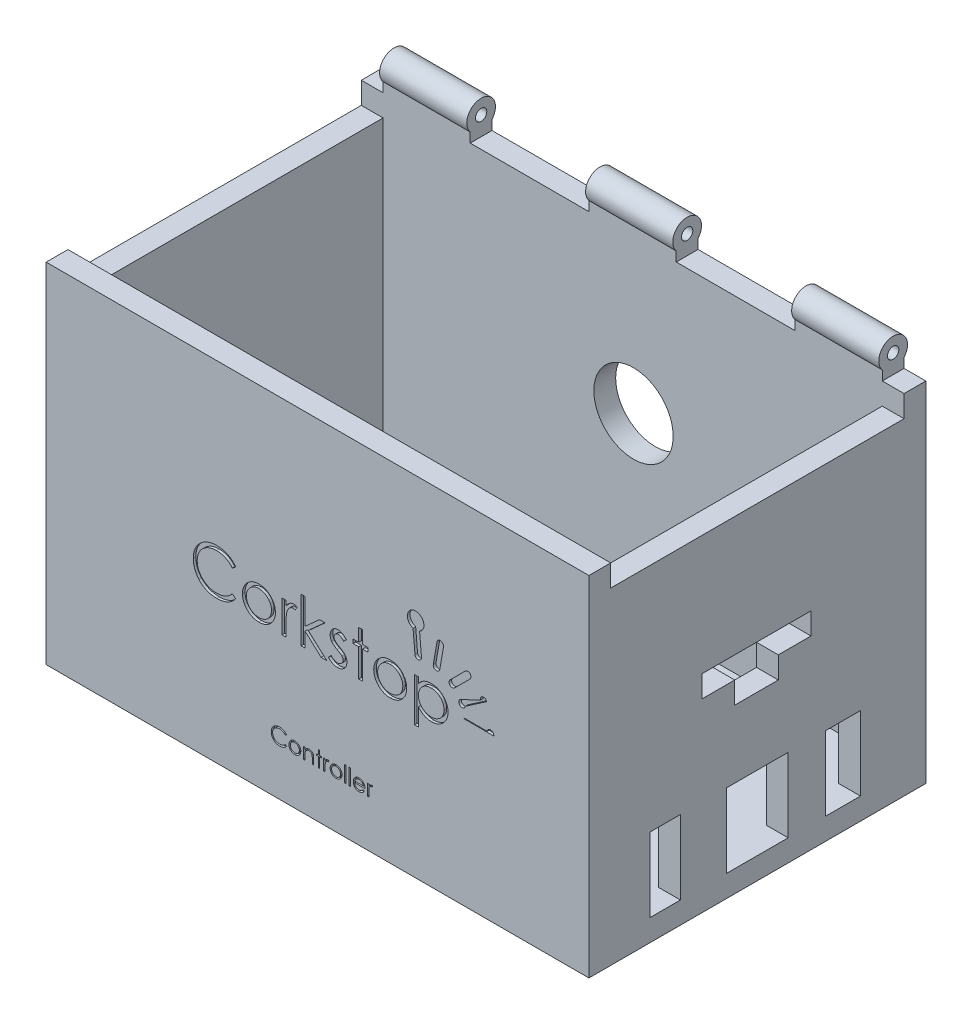
SolidWorks part; units mm, degrees
ref_plane "Front Plane" through (0, 0, 0) normal (0, 0, 1) x (1, 0, 0)
ref_plane "Top Plane" through (0, 0, 0) normal (0, 1, 0) x (1, 0, 0)
ref_plane "Right Plane" through (0, 0, 0) normal (1, 0, 0) x (0, 0, -1)
sketch "Sketch1" plane through (0, 0, 0) normal (0, 1, 0) x (1, 0, 0)
  line L1 (-79.1, 49.1) -> (79.1, 49.1)
  line L2 (-79.1, 49.1) -> (-79.1, -49.1)
  line L3 (-79.1, -49.1) -> (79.1, -49.1)
  line L4 (79.1, 49.1) -> (79.1, -49.1)
  line L5 (-79.1, 49.1) -> (79.1, -49.1) construction
  line L6 (-79.1, -49.1) -> (79.1, 49.1) construction
  point P0 (0, 0)
  dimension "D1" = 158.2
  dimension "D2" = 98.2
extrude "Boss-Extrude1" add sketch "Sketch1" along normal blind 6.35
sketch "Sketch2" plane through (0, 0, 49.1) normal (0, 0, 1) x (1, 0, 0)
  line L1 (-79.1, 101.6) -> (79.1, 101.6)
  line L2 (-79.1, 101.6) -> (-79.1, 6.35)
  line L3 (-79.1, 6.35) -> (79.1, 6.35)
  line L4 (79.1, 101.6) -> (79.1, 6.35)
  line L5 (-79.1, 101.6) -> (79.1, 6.35) construction
  line L6 (-79.1, 6.35) -> (79.1, 101.6) construction
  point P0 (0, 53.975)
  dimension "D1" = 95.25
extrude "Boss-Extrude2" add sketch "Sketch2" against normal blind 6.35
sketch "Sketch3" plane through (-79.1, 0, 0) normal (-1, 0, 0) x (0, 0, 1)
  line L1 (-42.75, 101.6) -> (42.75, 101.6)
  line L2 (-42.75, 101.6) -> (-42.75, 6.35)
  line L3 (-42.75, 6.35) -> (42.75, 6.35)
  line L4 (42.75, 101.6) -> (42.75, 6.35)
  line L5 (-42.75, 101.6) -> (42.75, 6.35) construction
  line L6 (-42.75, 6.35) -> (42.75, 101.6) construction
  point P0 (0, 53.975)
  dimension "D1" = 95.25
extrude "Boss-Extrude3" add sketch "Sketch3" against normal blind 6.35
sketch "Sketch4" plane through (0, 0, -49.1) normal (0, 0, -1) x (-1, 0, 0)
  line L1 (-79.1, 101.6) -> (79.1, 101.6)
  line L2 (-79.1, 101.6) -> (-79.1, 6.35)
  line L3 (-79.1, 6.35) -> (79.1, 6.35)
  line L4 (79.1, 101.6) -> (79.1, 6.35)
  line L5 (-79.1, 101.6) -> (79.1, 6.35) construction
  line L6 (-79.1, 6.35) -> (79.1, 101.6) construction
  point P0 (0, 53.975)
  dimension "D1" = 95.25
extrude "Boss-Extrude4" add sketch "Sketch4" against normal blind 6.35
sketch "Sketch5" plane through (79.1, 0, 0) normal (1, 0, 0) x (0, 0, -1)
  line L0 (42.75, 101.6) -> (42.75, 6.35) construction
  line L1 (-42.75, 27.94) -> (42.75, 27.94)
  line L2 (-42.75, 27.94) -> (-42.75, 101.6)
  line L3 (-42.75, 101.6) -> (42.75, 101.6)
  line L4 (42.75, 27.94) -> (42.75, 101.6)
  line L5 (-42.75, 27.94) -> (42.75, 101.6) construction
  line L6 (-42.75, 101.6) -> (42.75, 27.94) construction
  line L7 (42.75, 101.6) -> (42.75, 6.35) construction
  line L8 (42.75, 101.6) -> (49.1, 101.6) construction
  point P0 (0, 64.77)
  dimension "D1" = 73.66
  dimension "D2" = 0
extrude "Boss-Extrude5" add sketch "Sketch5" against normal blind 6.35
sketch "Sketch6" plane through (79.1, 0, 0) normal (1, 0, 0) x (0, 0, -1)
  line L0 (-42.75, 27.94) -> (42.75, 27.94) construction
  line L1 (-22.43, 27.94) -> (-8.968, 27.94)
  line L2 (-22.43, 27.94) -> (-22.43, 6.35)
  line L3 (-22.43, 6.35) -> (-8.968, 6.35)
  line L4 (-8.968, 27.94) -> (-8.968, 6.35)
  line L5 (-42.75, 6.35) -> (42.75, 6.35) construction
  line L6 (42.75, 6.35) -> (-42.75, 6.35) construction
  line L7 (8.968, 27.94) -> (19.89, 27.94)
  line L8 (8.968, 27.94) -> (8.968, 6.35)
  line L9 (8.968, 6.35) -> (19.89, 6.35)
  line L10 (19.89, 27.94) -> (19.89, 6.35)
  line L11 (-42.75, 6.35) -> (-42.75, 27.94) construction
  line L12 (42.75, 27.94) -> (42.75, 6.35) construction
  line L14 (-42.75, 27.94) -> (-31.32, 27.94)
  line L15 (-42.75, 27.94) -> (-42.75, 6.35)
  line L16 (-42.75, 6.35) -> (-31.32, 6.35)
  line L17 (-31.32, 27.94) -> (-31.32, 6.35)
  line L18 (42.75, 27.94) -> (30.05, 27.94)
  line L19 (42.75, 27.94) -> (42.75, 6.35)
  line L20 (42.75, 6.35) -> (30.05, 6.35)
  line L21 (30.05, 27.94) -> (30.05, 6.35)
  dimension "D1" = 13.462
  dimension "D2" = 10.922
  dimension "D3" = 20.32
  dimension "D4" = 22.86
  dimension "D5" = 0
  dimension "D6" = 11.43
  dimension "D7" = 12.7
  dimension "D8" = 17.936
extrude "Boss-Extrude6" add sketch "Sketch6" against normal blind 6.35
sketch "Çizim2" plane through (79.1, 0, 0) normal (1, 0, 0) x (0, 0, -1)
  line L0 (-49.1, 0) -> (49.1, 0) construction
  line L1 (-16.125, 60.325) -> (15.625, 60.325)
  line L2 (-16.125, 60.325) -> (-16.125, 53.975)
  line L3 (-16.125, 53.975) -> (-6.6, 53.975)
  line L4 (15.625, 60.325) -> (15.625, 53.975)
  line L5 (-16.125, 60.325) -> (15.625, 53.975) construction
  line L6 (-16.125, 53.975) -> (15.625, 60.325) construction
  line L7 (-42.75, 101.6) -> (-42.75, 6.35) construction
  line L8 (6.1, 53.975) -> (15.625, 53.975)
  line L9 (-6.6, 47.625) -> (6.1, 47.625)
  line L10 (-6.6, 47.625) -> (-6.6, 53.975)
  line L12 (6.1, 47.625) -> (6.1, 53.975)
  line L13 (-6.6, 47.625) -> (-0.25, 50.8) construction
  line L14 (-6.6, 53.975) -> (6.1, 47.625) construction
  point P0 (-0.25, 57.15)
  point P9 (-0.25, 50.8)
  dimension "D1" = 60.325
  dimension "D2" = 53.975
  dimension "D3" = 31.75
  dimension "D4" = 42.5
  dimension "D5" = 12.7
  dimension "D6" = 42.5
  dimension "D7" = 6.35
extrude "Kes-Ekstrüzyon1" cut sketch "Çizim2" against normal blind 6.35
sketch "Çizim3" plane through (0, 0, -49.1) normal (0, 0, -1) x (-1, 0, 0)
  line L0 (-79.1, 0) -> (79.1, 0) construction
  line L1 (-79.1, 101.6) -> (-79.1, 0) construction
  circle A0 centre (-0.25, 57.15) radius 11.557
  dimension "D1" = 23.114
  dimension "D2" = 57.15
  dimension "D3" = 78.85
extrude "Kes-Ekstrüzyon2" cut sketch "Çizim3" against normal blind 6.35
sketch "Çizim4" plane through (-79.1, 0, 0) normal (-1, 0, 0) x (0, 0, 1)
  line L0 (-49.1, 0) -> (49.1, 0) construction
  circle A0 centre (0, 41.275) radius 4.826
  dimension "D1" = 41.275
extrude "Kes-Ekstrüzyon3" cut sketch "Çizim4" against normal blind 6.35
sketch "Çizim5" plane through (79.1, 0, 0) normal (1, 0, 0) x (0, 0, -1)
  line L0 (42.75, 6.35) -> (42.75, 101.6) construction
  line L1 (-42.75, 101.6) -> (42.75, 101.6)
  line L2 (-42.75, 101.6) -> (-42.75, 95.25)
  line L3 (-42.75, 95.25) -> (42.75, 95.25)
  line L4 (42.75, 101.6) -> (42.75, 95.25)
  dimension "D1" = 6.35
extrude "Kes-Ekstrüzyon4" cut sketch "Çizim5" against normal blind 6.35
sketch "Çizim6" plane through (-79.1, 0, 0) normal (-1, 0, 0) x (0, 0, 1)
  line L1 (-42.75, 101.6) -> (42.75, 101.6)
  line L2 (-42.75, 101.6) -> (-42.75, 95.25)
  line L3 (-42.75, 95.25) -> (42.75, 95.25)
  line L4 (42.75, 101.6) -> (42.75, 95.25)
extrude "Kes-Ekstrüzyon5" cut sketch "Çizim6" against normal blind 6.35
sketch "Çizim7" plane through (0, 0, 49.1) normal (0, 0, 1) x (1, 0, 0)
  line L0 (-72.75, 6.35) -> (-72.75, 95.25) construction
  line L1 (-72.75, 6.35) -> (72.75, 6.35) construction
  text T0 "Corkstop" font "Century Gothic" height 12.7
  dimension "D1" = 35.56
  dimension "D2" = 35.56
extrude "Kes-Ekstrüzyon6" cut sketch "Çizim7" against normal blind 0.762
sketch "Çizim12" plane through (0, 0, 49.1) normal (0, 0, 1) x (1, 0, 0)
  line L2 (27.8371, 62.676) -> (28.3905, 56.3502)
  line L4 (29.7431, 62.8428) -> (30.2966, 56.517)
  arc A1 (28.3905, 56.3502) -> (30.2966, 56.517) centre (29.3435, 56.4336) ccw
  arc A2 (29.7431, 62.8428) -> (27.8371, 62.676) centre (28.5971, 64.966) ccw
  dimension "D1" = 3.81
  dimension "D2" = 6.35
  dimension "D3" = 1.9133
  dimension "D4" = 6.35
  dimension "D5" = 6.35
extrude "Kes-Ekstrüzyon7" cut sketch "Çizim12" against normal blind 0.762
sketch "Çizim14" plane through (0, 0, 49.1) normal (0, 0, 1) x (1, 0, 0)
  line L1 (43.1131, 47.4484) -> (49.4631, 47.4484)
  line L3 (42.4975, 47.2249) -> (51.3633, 47.2249)
  arc A0 (51.3633, 47.2249) -> (49.4631, 47.4484) centre (50.4132, 47.3366) ccw
  arc A1 (43.1131, 47.4484) -> (42.4975, 47.2249) centre (43.1131, 46.489) ccw
  dimension "D1" = 1.9133
  dimension "D2" = 6.35
  dimension "D3" = 5.08
extrude "Kes-Ekstrüzyon8" cut sketch "Çizim14" against normal blind 0.762
sketch "Çizim15" plane through (0, 0, 49.1) normal (0, 0, 1) x (1, 0, 0)
  line L0 (41.7144, 51.6199) -> (47.4695, 54.3035)
  line L1 (43.0621, 50.5695) -> (49.3029, 54.8505)
  line L2 (49.4631, 47.4484) -> (43.1131, 47.4484) construction
  arc A0 (49.3029, 54.8505) -> (47.4695, 54.3035) centre (48.3862, 54.577) ccw
  arc A1 (41.7144, 51.6199) -> (43.0621, 50.5695) centre (42.1199, 50.7504) ccw
  dimension "D1" = 1.9133
  dimension "D2" = 6.35
  dimension "D3" = 5.842
  dimension "D4" = 3.302
extrude "Kes-Ekstrüzyon9" cut sketch "Çizim15" against normal blind 0.762
sketch "Çizim18" plane through (0, 0, 49.1) normal (0, 0, 1) x (1, 0, 0)
  line L0 (38.6008, 54.9998) -> (43.0909, 59.4899)
  line L1 (39.8809, 53.5741) -> (44.4438, 58.137)
  arc A0 (44.4438, 58.137) -> (43.0909, 59.4899) centre (43.7674, 58.8135) ccw
  arc A1 (38.6008, 54.9998) -> (39.8809, 53.5741) centre (39.2792, 54.3214) ccw
  dimension "D1" = 1.9133
  dimension "D2" = 6.35
sketch "Çizim19" plane through (0, 0, 49.1) normal (0, 0, 1) x (1, 0, 0)
  line L0 (33.7349, 56.4717) -> (34.8376, 62.7252)
  line L1 (35.6013, 56.0381) -> (36.7218, 62.393)
  arc A0 (36.7218, 62.393) -> (34.8376, 62.7252) centre (35.7797, 62.5591) ccw
  arc A1 (33.7349, 56.4717) -> (35.6013, 56.0381) centre (34.6798, 56.3051) ccw
  dimension "D1" = 1.9133
  dimension "D2" = 6.35
extrude "Kes-Ekstrüzyon12" cut sketch "Çizim19" against normal blind 0.762
extrude "Kes-Ekstrüzyon13" cut sketch "Çizim18" against normal blind 0.762
sketch "Çizim27" plane through (0, 0, 49.1) normal (0, 0, 1) x (1, 0, 0)
  text T0 "Controller\r\n" font "Century Gothic" height 4.572
sketch "Çizim21" plane through (-72.75, 0, 0) normal (1, 0, 0) x (0, 0, -1)
  line L1 (42.75, 101.6) -> (49.1, 101.6)
  line L2 (42.75, 101.6) -> (42.75, 104.3997)
  line L4 (49.1, 101.6) -> (49.1, 104.3997)
  arc A0 (49.1, 104.3997) -> (42.75, 104.3997) centre (45.925, 107.1365) ccw
  dimension "D1" = 6.35
  dimension "D2" = 3.175
extrude "Yükseklik-Ekstrüzyon2" add sketch "Çizim21" along normal blind 25.4
sketch "Çizim22" plane through (72.75, 0, 0) normal (-1, 0, 0) x (0, 0, 1)
  line L0 (-49.1, 101.6) -> (-42.75, 101.6)
  line L1 (-49.1, 101.6) -> (-49.1, 104.3995)
  line L2 (-42.75, 101.6) -> (-42.75, 104.3995)
  arc A0 (-42.75, 104.3995) -> (-49.1, 104.3995) centre (-45.925, 107.1364) ccw
  dimension "D1" = 6.35
  dimension "D2" = 3.175
extrude "Yükseklik-Ekstrüzyon3" add sketch "Çizim22" along normal blind 25.4
ref_plane "Düzlem2" through (12.7, 0, 0) normal (-1, 0, 0) x (0, 0, 1)
sketch "Çizim23" plane through (12.7, 0, 0) normal (-1, 0, 0) x (0, 0, 1)
  line L0 (-49.1, 101.6) -> (-42.75, 101.6)
  line L1 (-49.1, 101.6) -> (-49.1, 104.3997)
  line L2 (-42.75, 101.6) -> (-42.75, 104.3997)
  arc A0 (-42.75, 104.3997) -> (-49.1, 104.3997) centre (-45.925, 107.1365) ccw
  dimension "D1" = 6.35
  dimension "D2" = 3.175
extrude "Yükseklik-Ekstrüzyon4" add sketch "Çizim23" along normal blind 25.4
extrude "Yükseklik-Ekstrüzyon5" add sketch "Çizim23<2>" along normal blind 12.7
sketch "Çizim23<2>" plane through (12.7, 0, 0) normal (-1, 0, 0) x (0, 0, 1) same geometry as "Çizim23"
sketch "Çizim24" plane through (12.7, 0, 0) normal (-1, 0, 0) x (0, 0, 1)
  circle A0 centre (-45.925, 107.1365) radius 1.651
extrude "Kes-Ekstrüzyon14" cut sketch "Çizim24" along normal blind 25.4 contours A0
sketch "Çizim25" plane through (72.75, 0, 0) normal (1, 0, 0) x (0, 0, -1)
  circle A0 centre (45.925, 107.1364) radius 1.651
extrude "Kes-Ekstrüzyon15" cut sketch "Çizim25" against normal blind 25.4
sketch "Çizim26" plane through (-72.75, 0, 0) normal (-1, 0, 0) x (0, 0, 1)
  circle A0 centre (-45.925, 107.1365) radius 1.651
extrude "Kes-Ekstrüzyon16" cut sketch "Çizim26" against normal blind 25.4
extrude "Kes-Ekstrüzyon17" cut sketch "Çizim27" against normal blind 0.762
